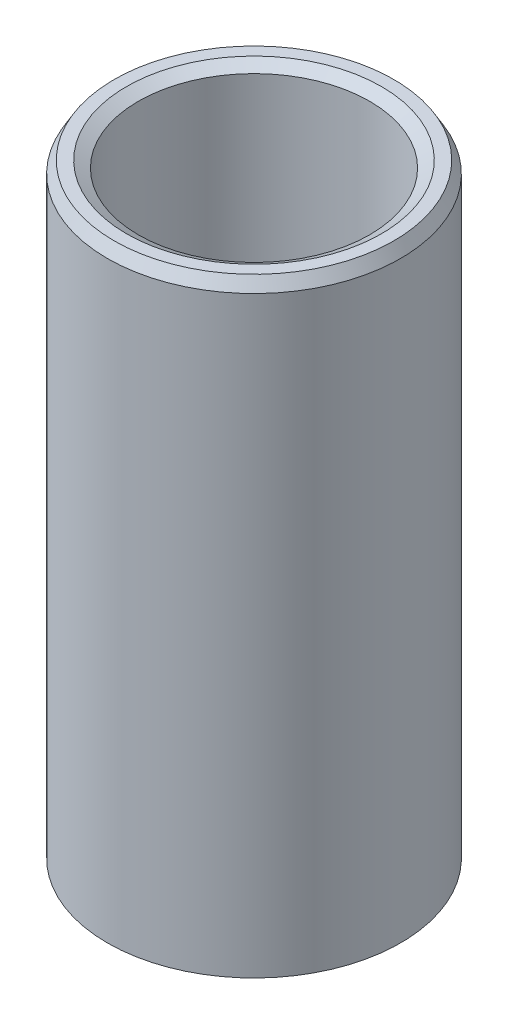
SolidWorks part; units mm, degrees
ref_plane "Front Plane" through (0, 0, 0) normal (0, 0, 1) x (1, 0, 0)
ref_plane "Top Plane" through (0, 0, 0) normal (0, 1, 0) x (1, 0, 0)
ref_plane "Right Plane" through (0, 0, 0) normal (1, 0, 0) x (0, 0, -1)
sketch "Sketch1" plane through (0, 0, 0) normal (0, 1, 0) x (1, 0, 0)
  circle A0 centre (0, 0) radius 20
  dimension "SLEEVE_OD" = 40
extrude "Boss-Extrude1" add sketch "Sketch1" along normal blind 83.3828
sketch "Sketch2" plane through (0, 0, 0) normal (0, 1, 0) x (1, 0, 0)
  circle A0 centre (0, 0) radius 15.7768
  dimension "BORE_D" = 31.5536
extrude "Cut-Extrude1" cut sketch "Sketch2" along normal through all
chamfer "Chamfer1" distance 1.6125 angle 30 4 edges at (0, 83.3828, 15.7768) (0, 0, 15.7768) (0, 0, 20) (0, 83.3828, 20) first distance on face at (0, 83.3828, 15.7768) first distance on face at (0, 0, 15.7768) first distance on face at (0, 83.3828, 20)
